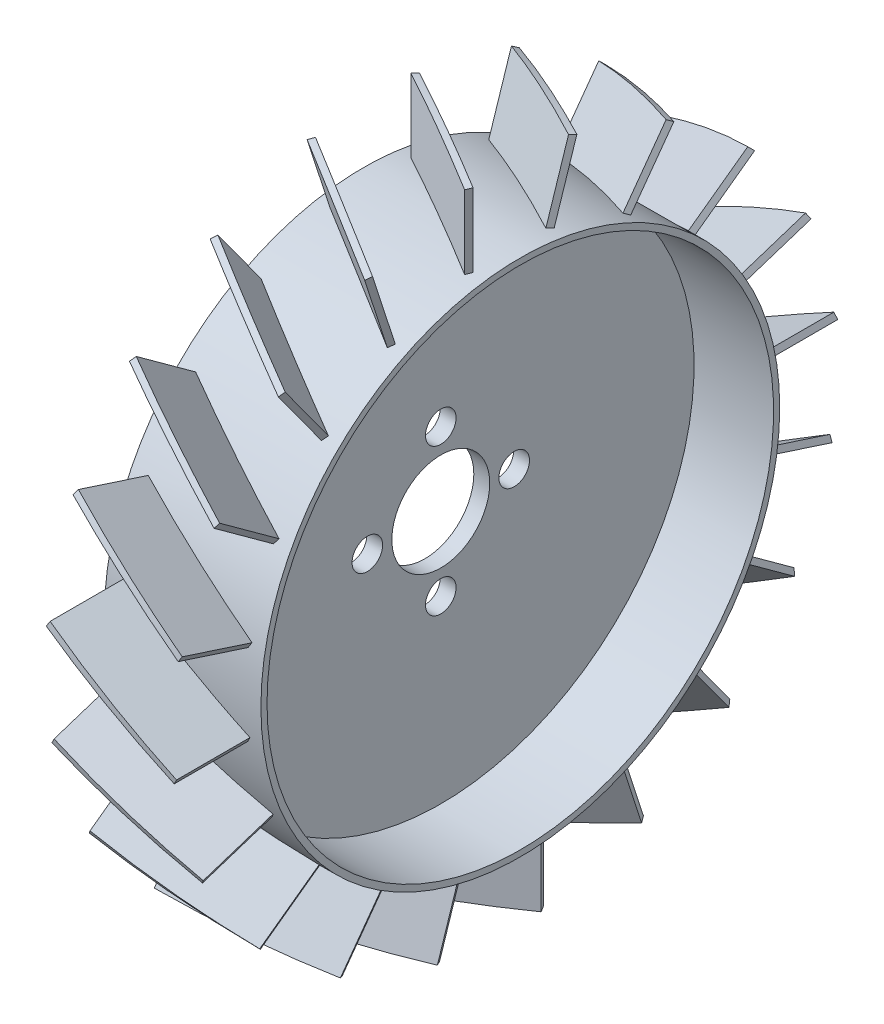
SolidWorks part; units mm, degrees
ref_plane "Front Plane" through (0, 0, 0) normal (0, 0, 1) x (1, 0, 0)
ref_plane "Top Plane" through (0, 0, 0) normal (0, 1, 0) x (1, 0, 0)
ref_plane "Right Plane" through (0, 0, 0) normal (1, 0, 0) x (0, 0, -1)
sketch "Sketch1" plane through (0, 0, 0) normal (0, 1, 0) x (1, 0, 0)
  line L0 (3.302, 0) -> (3.302, 52.578)
  line L1 (3.302, 52.578) -> (19.812, 52.578)
  line L2 (19.812, 52.578) -> (19.812, 53.848)
  line L3 (19.812, 53.848) -> (-12.7, 53.848)
  line L4 (-12.7, 53.848) -> (-12.7, 52.578)
  line L5 (-12.7, 52.578) -> (0, 52.578)
  line L6 (0, 52.578) -> (0, 0)
  line L7 (0, 0) -> (3.302, 0)
  dimension "D1" = 3.302
  dimension "D2" = 1.27
  dimension "D3" = 52.578
  dimension "D4" = 32.512
  dimension "D5" = 12.7
revolve "Revolve1" add sketch "Sketch1" angle 360 about L7
ref_plane "Plane1" through (0, 0, 83.82) normal (0, 0, 1) x (1, 0, 0)
sketch "Sketch2" plane through (0, 0, 83.82) normal (0, 0, 1) x (1, 0, 0)
  line L0 (-9.9597, 7.0701) -> (16.4367, -8.1699)
  line L1 (16.4367, -8.1699) -> (17.0717, -7.0701)
  line L3 (17.0717, -7.0701) -> (-9.3247, 8.1699)
  line L4 (-9.3247, 8.1699) -> (-9.9597, 7.0701)
  line L5 (-12.7, 0) -> (19.812, 0) construction
  line L6 (-12.7, 53.848) -> (-12.7, -53.848) construction
  line L7 (19.812, -53.848) -> (19.812, 53.848) construction
  line L8 (3.2385, -0.5499) -> (3.8735, 0.5499) construction
  point P4 (3.556, 0)
  point P13 (3.556, 0)
  dimension "D1" = 1.27
  dimension "D2" = 30
  dimension "D3" = 30.48
extrude "Boss-Extrude1" add sketch "Sketch2" along normal blind 15.24 from surface starting at face at (-12.7, 0, 53.848)
pattern_circular "CirPattern15" count 20 over 360 about axis through (19.812, 0, 0) along (-1, 0, 0) of "Boss-Extrude1"
sketch "Sketch7" plane through (3.302, 0, 0) normal (1, 0, 0) x (0, 0, -1)
  circle A0 centre (0, 15.24) radius 3.175
  circle A1 centre (0, 0) radius 10.16
  circle A2 centre (15.24, 0) radius 3.175
  circle A3 centre (0, -15.24) radius 3.175
  circle A4 centre (-15.24, 0) radius 3.175
  point P14 (0, 0)
  dimension "D1" = 6.35
  dimension "D3" = 20.32
  dimension "D2" = 15.24
  dimension "D4" = 4
extrude "Cut-Extrude1" cut sketch "Sketch7" against normal through all
